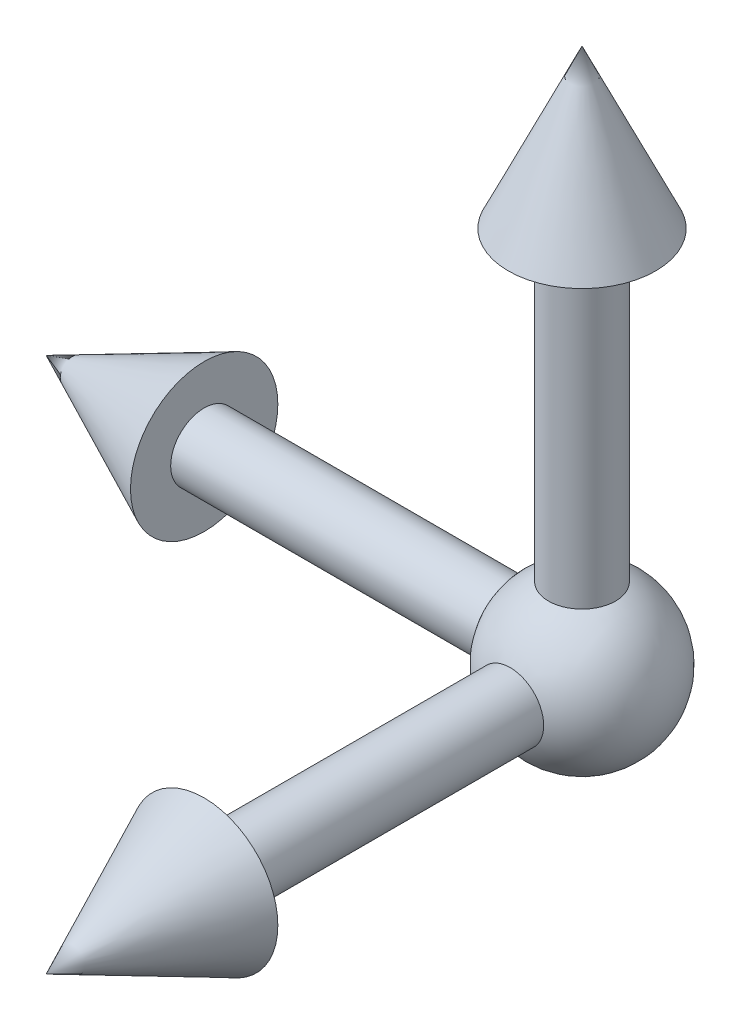
SolidWorks part; units mm, degrees
note: '?' marks a value the reader was unsure of.
ref_plane "Front Plane" through (0, 0, 0) normal (0, 0, 1) x (1, 0, 0)
ref_plane "Top Plane" through (0, 0, 0) normal (0, 1, 0) x (1, 0, 0)
ref_plane "Right Plane" through (0, 0, 0) normal (1, 0, 0) x (0, 0, -1)
sketch "Sketch1" plane through (0, 0, 0) normal (0, 0, 1) x (1, 0, 0)
  line L0 (0, 0) -> (36.9413, 0) construction
  line L1 (0, 0) -> (0, 12.5)
  line L2 (0, 12.5) -> (-141.0261, 12.5)
  line L3 (-141.0261, 12.5) -> (-141.0261, 27.5)
  line L4 (-141.0261, 27.5) -> (-200, 0)
  line L5 (-200, 0) -> (0, 0)
  dimension "D1" = 200
  dimension "D2" = 25
  dimension "D3" = 55
  dimension "D4" = 25
revolve "Revolve1" add sketch "Sketch1" angle 360 about L0
ref_axis "Axis1" through (0, 30.25, 0) along (0, -1, 0)?
pattern_circular "CirPattern1" count 2 every 90 about axis through (0, 30.25, 0) along (0, -1, 0) of "Revolve1"
ref_axis "Axis2" through (0, 0, -36.375) along (0, 0, 1)?
pattern_circular "CirPattern2" count 2 every 90 about axis through (0, 0, -36.375) along (0, 0, 1) of "Revolve1"
sketch "Sketch2" plane through (0, 0, 0) normal (0, 0, 1) x (1, 0, 0)
  line L0 (-29.5834, 0) -> (29.5834, 0)
  arc A0 (-29.5834, 0) -> (29.5834, 0) centre (0, 0) ccw
revolve "Revolve2" add sketch "Sketch2" angle 360 about L0
